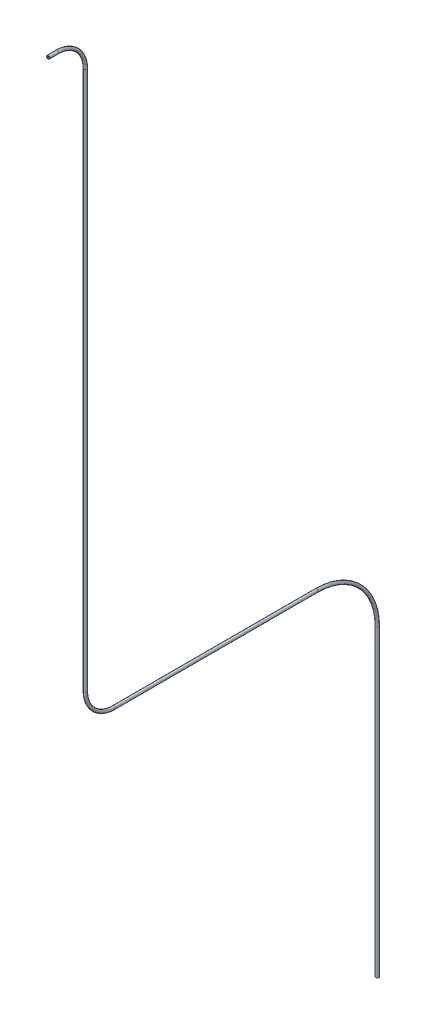
SolidWorks part; units mm, degrees
ref_plane "Front" through (0, 0, 0) normal (0, 0, 1) x (1, 0, 0)
ref_plane "Top" through (0, 0, 0) normal (0, 1, 0) x (1, 0, 0)
ref_plane "Right" through (0, 0, 0) normal (1, 0, 0) x (0, 0, -1)
sketch3d "3DSketch1"
  line L0 (0, 0, 0) -> (0, 0, -2.2)
  line L1 (0, -7, -9.2) -> (0, -140, -9.2)
  line L2 (0, -147, -16.2) -> (0, -147, -66.2)
  line L3 (0, -162, -81.2) -> (0, -237, -81.2)
  arc A2 (0, 0, -2.2) -> (0, -7, -9.2) centre (0, -7, -2.2) ccw
  arc A3 (0, -140, -9.2) -> (0, -147, -16.2) centre (0, -140, -16.2) ccw
  arc A4 (0, -147, -66.2) -> (0, -162, -81.2) centre (0, -162, -66.2) ccw
  point P2 (7, -140, -16.2)
  point P8 (-7, -7, -2.2)
  point P11 (-15, -162, -66.2)
  dimension "D1" = 90
  dimension "D7" = 50
  dimension "D2" = 7
  dimension "D3" = 7
  dimension "D8" = 75
  dimension "D4" = 2.2
  dimension "D5" = 90
  dimension "D6" = 140
  dimension "D9" = 90
  dimension "D10" = 15
sweep "Sweep-Thin1" add path "3DSketch1" circular profile diameter 0.38 parameters "D1"=0.2, "D3"=0.38
ref_plane "Plane1" through (0, 0, -9.2) normal (0, 0, 1) x (1, 0, 0)
